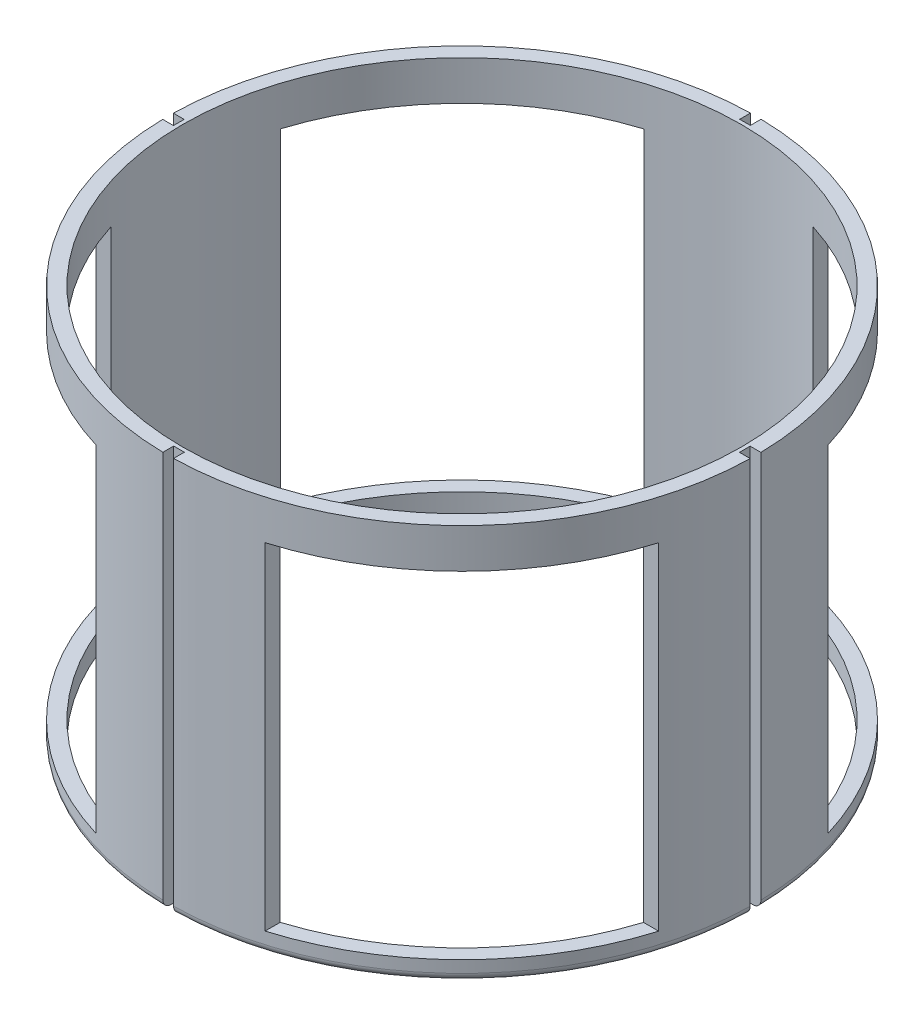
SolidWorks part; units mm, degrees
ref_plane "Front" through (0, 0, 0) normal (0, 0, 1) x (1, 0, 0)
ref_plane "Top" through (0, 0, 0) normal (0, 1, 0) x (1, 0, 0)
ref_plane "Right" through (0, 0, 0) normal (1, 0, 0) x (0, 0, -1)
sketch "Sketch1" plane through (0, 0, 0) normal (0, 1, 0) x (1, 0, 0)
  circle A0 centre (0, 0) radius 89.662
  circle A1 centre (0, 0) radius 94.2975
  dimension "Inner Diameter" = 179.324
  dimension "Outer Diameter" = 188.595
extrude "Boss-Extrude1" add sketch "Sketch1" against normal blind 127
sketch "Sketch5" plane through (0, 0, 0) normal (0, 1, 0) x (1, 0, 0)
  line L0 (0, 114.2751) -> (0, -136.7211) construction
  line L1 (-124.857, 0) -> (116.4345, 0) construction
  line L2 (-1.7145, 90.8209) -> (1.7145, 90.8209)
  line L3 (1.7145, 90.8209) -> (1.7145, 95.9009)
  line L4 (1.7145, 95.9009) -> (-1.7145, 95.9009)
  line L5 (-1.7145, 95.9009) -> (-1.7145, 90.8209)
  line L6 (1.7145, -95.9009) -> (-1.7145, -95.9009)
  line L7 (1.7145, -90.8209) -> (1.7145, -95.9009)
  line L8 (-1.7145, -90.8209) -> (1.7145, -90.8209)
  line L9 (-1.7145, -95.9009) -> (-1.7145, -90.8209)
  line L10 (-90.8209, 1.651) -> (-90.8209, -1.778)
  line L11 (-90.8209, -1.778) -> (-95.9009, -1.778)
  line L12 (-95.9009, -1.778) -> (-95.9009, 1.651)
  line L13 (-95.9009, 1.651) -> (-90.8209, 1.651)
  line L14 (95.9009, -1.778) -> (95.9009, 1.651)
  line L15 (90.8209, -1.778) -> (95.9009, -1.778)
  line L16 (90.8209, 1.651) -> (90.8209, -1.778)
  line L17 (95.9009, 1.651) -> (90.8209, 1.651)
  dimension "D1" = 1.7145
  dimension "D2" = 1.7145
  dimension "D3" = 5.08
  dimension "D4" = 90.8209
  dimension "D5" = 1.651
  dimension "D6" = 90.8209
extrude "Cut-Extrude1" cut sketch "Sketch5" against normal blind 127
sketch "Sketch7" plane through (0, 0, 0) normal (0, 1, 0) x (1, 0, 0)
  line L0 (85.4437, -27.178) -> (90.296, -27.178)
  line L1 (27.1145, -85.4639) -> (27.1145, -90.3151)
  line L2 (1.7145, -94.2819) -> (1.7145, -90.8209) construction
  line L3 (90.8209, -1.778) -> (94.2807, -1.778) construction
  arc A0 (85.4437, -27.178) -> (27.1145, -85.4639) centre (0, 0) cw
  circle A1 centre (0, 0) radius 89.662 construction
  arc A2 (90.296, -27.178) -> (27.1145, -90.3151) centre (0, 0) cw
  arc A3 (1.7145, -94.2819) -> (94.2807, -1.778) centre (0, 0) ccw construction
  point P15 (92.5508, -1.778)
  dimension "D3" = 94.2975
  dimension "D4" = 89.662
  dimension "D1" = 25.4
  dimension "D2" = 25.4
extrude "Cut-Extrude2" cut sketch "Sketch7" against normal blind 107.95 from offset 12.7 offset against normal yes
pattern_circular "CirPattern1" count 4 over 360 about axis through (0, 0, 0) along (0, 1, 0) of "Cut-Extrude2"
fillet "Fillet1" radius 2.54 4 edges at (-66.7009, -127, -66.6559) (-66.6559, -127, 66.7009) (66.7009, -127, -66.6559) (66.6559, -127, 66.7009)
equation "\"D4@Sketch5\"=(\"Inner Diameter\"/2)+((\"Outer Diameter\"-\"Inner Diameter\")/8)"
equation "\"D6@Sketch5\"=(\"Inner Diameter\"/2)+((\"Outer Diameter\"-\"Inner Diameter\")/8)"
equation "\"D1@Cut-Extrude1\"=\"Fin Length\""
equation "\"D3@Sketch7\"=\"Outer Diameter\"/2"
equation "\"D4@Sketch7\"=\"Inner Diameter\"/2"
